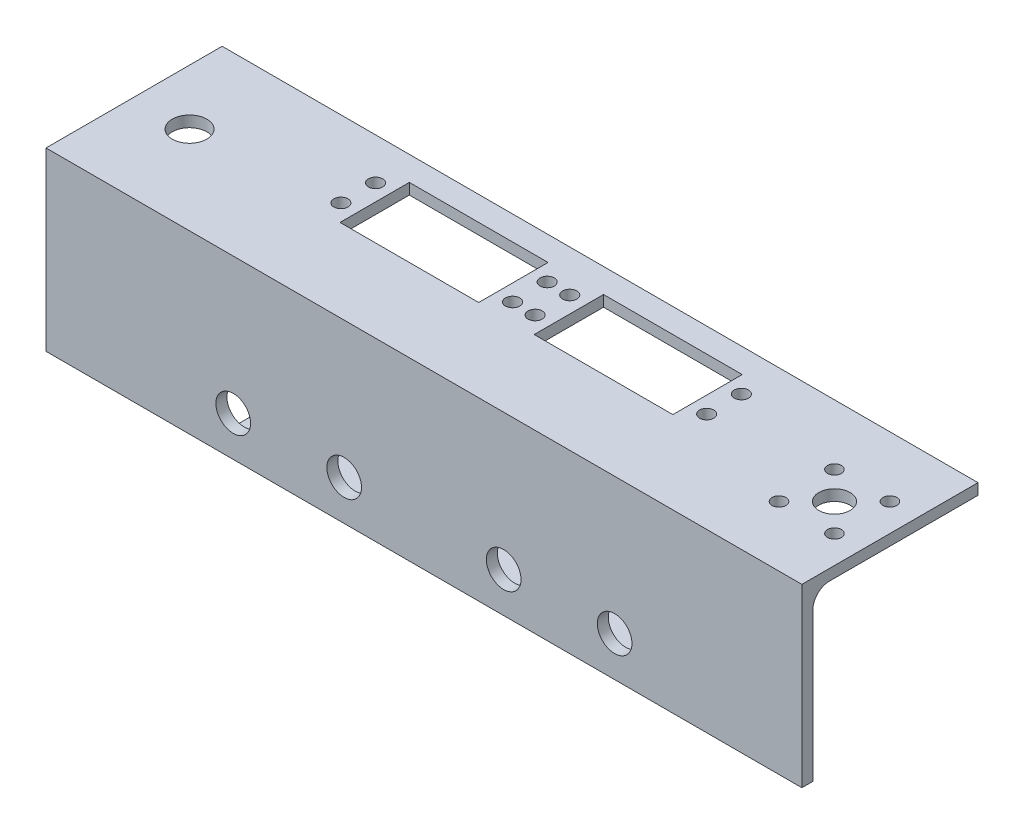
SolidWorks part; units mm, degrees
material "6061 Alloy"
ref_plane "Front Plane" through (0, 0, 0) normal (0, 0, 1) x (1, 0, 0)
ref_plane "Top Plane" through (0, 0, 0) normal (0, 1, 0) x (1, 0, 0)
ref_plane "Right Plane" through (0, 0, 0) normal (1, 0, 0) x (0, 0, -1)
sketch "Sketch1" plane through (0, 0, 0) normal (1, 0, 0) x (0, 0, -1)
  line L0 (0, 0) -> (50.8, 0)
  line L1 (50.8, 0) -> (50.8, -3.175)
  line L2 (50.8, -3.175) -> (3.175, -3.175)
  line L3 (3.175, -3.175) -> (3.175, -47.625)
  line L5 (0, -50.8) -> (0, 0)
  line L6 (0, -50.8) -> (50.8, -50.8)
  line L7 (50.8, -50.8) -> (50.8, -47.625)
  line L8 (50.8, -47.625) -> (3.175, -47.625)
  line L9 (3.175, -47.625) -> (0, -47.625) construction
  dimension "D1" = 50.8
extrude "Base Angle Profile" add sketch "Sketch1" along normal mid plane 218
sketch "Sketch2" plane through (0, 0, 0) normal (0, 1, 0) x (1, 0, 0)
  line L1 (-48, 43.8) -> (-8, 43.8)
  line L2 (-48, 43.8) -> (-48, 23.8)
  line L3 (-48, 23.8) -> (-8, 23.8)
  line L4 (-8, 43.8) -> (-8, 23.8)
  line L5 (-48, 43.8) -> (-8, 23.8) construction
  line L6 (-48, 23.8) -> (-8, 43.8) construction
  line L7 (8, 43.8) -> (48, 43.8)
  line L8 (8, 43.8) -> (8, 23.8)
  line L9 (8, 23.8) -> (48, 23.8)
  line L10 (48, 43.8) -> (48, 23.8)
  line L11 (8, 43.8) -> (48, 23.8) construction
  line L12 (8, 23.8) -> (48, 43.8) construction
  line L13 (-52.75, 38.8) -> (-52.75, 28.8) construction
  line L14 (-3.25, 28.8) -> (-3.25, 38.8) construction
  line L15 (3.25, 28.8) -> (3.25, 38.8) construction
  line L16 (52.75, 28.8) -> (52.75, 38.8) construction
  line L17 (109, 50.8) -> (-109, 50.8) construction
  line L18 (-3.25, 33.8) -> (3.25, 33.8) construction
  circle A0 centre (-52.75, 38.8) radius 2.05
  circle A1 centre (-52.75, 28.8) radius 2.05
  circle A2 centre (-3.25, 38.8) radius 2.05
  circle A3 centre (-3.25, 28.8) radius 2.05
  circle A4 centre (3.25, 28.8) radius 2.05
  circle A5 centre (3.25, 38.8) radius 2.05
  circle A6 centre (52.75, 38.8) radius 2.05
  circle A7 centre (52.75, 28.8) radius 2.05
  point P4 (-28, 33.8)
  point P9 (28, 33.8)
  point P10 (0, 33.8)
  point P28 (-52.75, 33.8)
  dimension "D5" = 4.1
  dimension "D1" = 20
  dimension "D2" = 40
  dimension "D3" = 16
  dimension "D6" = 4.75
  dimension "D7" = 10
  dimension "D8" = 4.75
  dimension "D9" = 4.75
  dimension "D10" = 4.75
  dimension "D11" = 7
extrude "Servo Mount Pattern" cut sketch "Sketch2" against normal up to surface (3.175 mm away) up to face at (0, -3.175, -26.9875)
fillet "Internal Fillet" radius 4.7752 1 edges at (0, -3.175, -3.175)
sketch "Sketch3" plane through (0, 0, 0) normal (0, 1, 0) x (1, 0, 0)
  line L0 (93, 25.4) -> (109, 25.4) construction
  line L1 (101, 33.4) -> (85, 33.4) construction
  line L2 (101, 33.4) -> (101, 17.4) construction
  line L3 (101, 17.4) -> (85, 17.4) construction
  line L4 (85, 33.4) -> (85, 17.4) construction
  line L5 (101, 33.4) -> (85, 17.4) construction
  line L6 (101, 17.4) -> (85, 33.4) construction
  line L7 (109, 50.8) -> (109, 0) construction
  line L10 (48, 23.8) -> (48, 43.8) construction
  circle A0 centre (93, 25.4) radius 4.5
  circle A1 centre (101, 33.4) radius 2
  circle A2 centre (85, 33.4) radius 2
  circle A3 centre (85, 17.4) radius 2
  circle A4 centre (101, 17.4) radius 2
  circle A5 centre (93, 25.4) radius 16 construction
  point P7 (93, 25.4)
  dimension "D1" = 4
  dimension "D2" = 9
  dimension "D6" = 32
  dimension "D3" = 16
  dimension "D4" = 16
  dimension "D5" = 45
extrude "Lead Screw Nut Pattern" cut sketch "Sketch3" against normal up to surface (3.175 mm away) up to face at (52.75, -3.175, -36.75)
sketch "Sketch4" plane through (0, 0, 0) normal (0, 1, 0) x (1, 0, 0)
  line L1 (93, 25.4) -> (-93, 25.4) construction
  circle A0 centre (-93, 25.4) radius 5
  circle A1 centre (-52.75, 28.8) radius 2.05 construction
  dimension "D1" = 10
  dimension "D2" = 40.25
extrude "Cut-Extrude3" cut sketch "Sketch4" against normal up to surface (3.175 mm away) up to face at (101, -3.175, -15.4)
sketch "Sketch5" plane through (0, -50.8, 0) normal (0, -1, 0) x (1, 0, 0)
  line L0 (-109, -3.175) -> (-60, -3.175)
  line L1 (-109, 0) -> (-109, -50.8) construction
  line L2 (-60, -3.175) -> (-60, -24.205)
  line L3 (-60, -24.205) -> (60, -24.205)
  line L4 (60, -24.205) -> (60, -3.175)
  line L5 (60, -3.175) -> (109, -3.175)
  line L6 (109, 0) -> (109, -50.8) construction
  line L7 (109, -3.175) -> (109, -50.8)
  line L8 (109, -50.8) -> (-109, -50.8)
  line L9 (-109, -50.8) -> (-109, -3.175)
  line L10 (109, 0) -> (-109, 0) construction
  point P16 (0, -24.205)
  dimension "D1" = 3.175
  dimension "D2" = 21.03
  dimension "D3" = 120
extrude "Channel Bottom Cut" cut sketch "Sketch5" against normal blind 10
sketch "Sketch7" plane through (0, 0, -3.175) normal (0, 0, -1) x (-1, 0, 0)
  line L0 (-60, -47.625) -> (60, -47.625) construction
  line L1 (-60, -47.625) -> (-60, -50.8) construction
  line L2 (60, -47.625) -> (60, -50.8) construction
  circle A0 centre (-55, -39.295) radius 5
  circle A1 centre (-23, -39.295) radius 5
  circle A2 centre (23, -39.295) radius 5
  circle A3 centre (55, -39.295) radius 5
  point P12 (48.5327, -39.295)
  dimension "D4" = 10
  dimension "D1" = 32
  dimension "D2" = 32
  dimension "D3" = 8.33
  dimension "D5" = 5
  dimension "D6" = 5
extrude "Cut-Extrude5" cut sketch "Sketch7" against normal through all
equation "\"Angle-Width\"= 25.4 * 2"
equation "\"D1@Sketch1\"=\"Angle-Width\""
equation "\"Angle-Thickness\"= 25.4 / 8"
equation "\"D8@Sketch2\"=\"D6@Sketch2\""
equation "\"D9@Sketch2\"=\"D6@Sketch2\""
equation "\"D10@Sketch2\"=\"D6@Sketch2\""
equation "\"D1@Sketch5\"=\"Angle-Thickness\""
